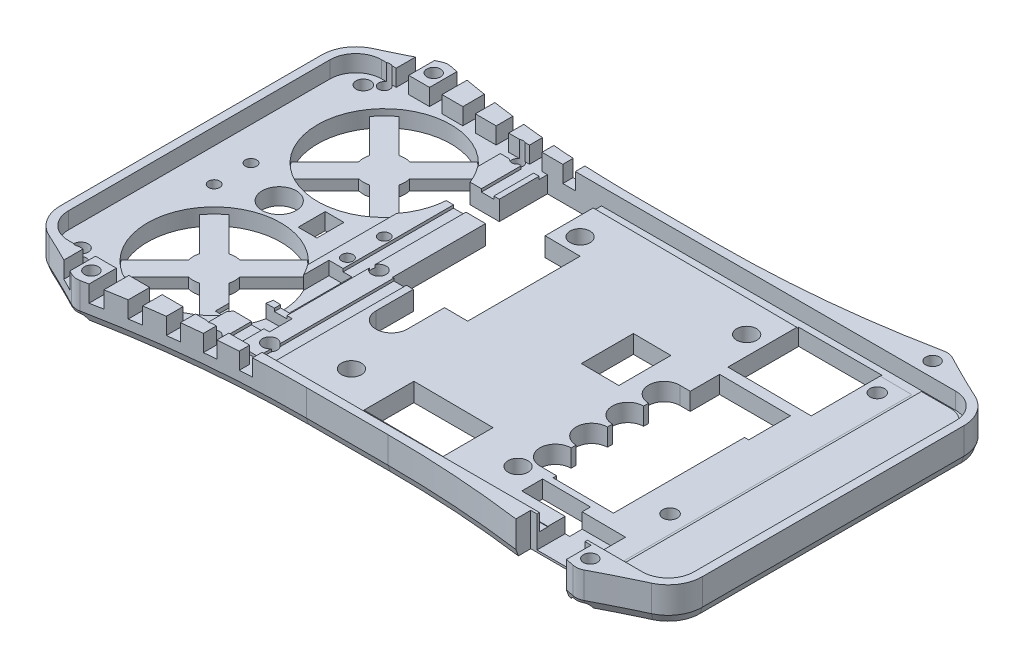
SolidWorks part; units mm, degrees
ref_plane "前视基准面" through (0, 0, 0) normal (0, 0, 1) x (1, 0, 0)
ref_plane "上视基准面" through (0, 0, 0) normal (0, 1, 0) x (1, 0, 0)
ref_plane "右视基准面" through (0, 0, 0) normal (1, 0, 0) x (0, 0, -1)
sketch "草图1" plane through (0, 0, 0) normal (0, 1, 0) x (1, 0, 0)
  line L0 (6, 0.2) -> (143.8, 0.2)
  line L1 (6, 0) -> (143.8, 0) construction
  line L2 (0, -6) -> (0, -68.8) construction
  line L3 (6, -74.8) -> (143.8, -74.8) construction
  line L4 (149.8, -6) -> (149.8, -68.8) construction
  line L5 (150, -6) -> (150, -68.8)
  line L6 (6, -75) -> (143.8, -75)
  line L7 (-0.2, -6) -> (-0.2, -68.8)
  arc A0 (143.8, 0) -> (149.8, -6) centre (143.8, -6) cw construction
  arc A1 (143.8, -74.8) -> (149.8, -68.8) centre (143.8, -68.8) ccw construction
  arc A2 (0, -68.8) -> (6, -74.8) centre (6, -68.8) ccw construction
  arc A3 (6, 0) -> (0, -6) centre (6, -6) ccw construction
  arc A4 (143.8, 0.2) -> (150, -6) centre (143.8, -6) cw
  arc A5 (143.8, -75) -> (150, -68.8) centre (143.8, -68.8) ccw
  arc A6 (-0.2, -68.8) -> (6, -75) centre (6, -68.8) ccw
  arc A7 (6, 0.2) -> (-0.2, -6) centre (6, -6) ccw
  point P7 (149.8, 0)
  point P12 (0, -74.8)
  point P15 (0, 0)
  dimension "D3" = 6
  dimension "D1" = 74.8
  dimension "D2" = 149.8
  dimension "D4" = 0.2
extrude "凸台-拉伸1" add sketch "草图1" along normal blind 4
sketch "草图2" plane through (0, 0, 0) normal (0, -1, 0) x (-1, 0, 0)
  line L0 (-122.6, -55.35) -> (-108.9, -55.35)
  line L1 (-122.6, -69.85) -> (-108.9, -69.85)
  line L2 (-122.6, -69.85) -> (-122.6, -63.95)
  line L3 (-122.6, -63.95) -> (-108.9, -63.95)
  line L4 (-108.9, -69.85) -> (-108.9, -63.95)
  line L5 (-135.3, -1.25) -> (-35.3, -1.25) construction
  line L6 (-135.3, -1.25) -> (-135.3, -73.55) construction
  line L7 (-135.3, -73.55) -> (-35.3, -73.55) construction
  line L8 (-35.3, -1.25) -> (-35.3, -73.55) construction
  line L9 (-108.9, -61.25) -> (-108.9, -55.35)
  line L10 (-122.6, -61.25) -> (-108.9, -61.25)
  line L11 (-122.6, -61.25) -> (-122.6, -55.35)
  line L12 (-122.6, -46.75) -> (-108.9, -46.75)
  line L13 (-108.9, -52.65) -> (-108.9, -46.75)
  line L14 (-122.6, -52.65) -> (-108.9, -52.65)
  line L15 (-122.6, -52.65) -> (-122.6, -46.75)
  line L16 (-122.6, -38.15) -> (-108.9, -38.15)
  line L17 (-108.9, -44.05) -> (-108.9, -38.15)
  line L18 (-122.6, -44.05) -> (-108.9, -44.05)
  line L19 (-122.6, -44.05) -> (-122.6, -38.15)
  line L20 (0, -6) -> (0, -68.8) construction
  line L21 (-35.3, -73.55) -> (-0.8, -73.55) construction
  line L22 (-120.25, -26.65) -> (-111.25, -26.65) construction
  line L23 (-120.25, -26.65) -> (-120.25, -33.15) construction
  line L24 (-120.25, -33.15) -> (-111.25, -33.15) construction
  line L25 (-111.25, -26.65) -> (-111.25, -33.15) construction
  line L26 (-85.8, -48.75) -> (-81.1, -48.75) construction
  line L27 (-85.8, -48.75) -> (-85.8, -58.15) construction
  line L28 (-85.8, -58.15) -> (-81.1, -58.15) construction
  line L29 (-81.1, -48.75) -> (-81.1, -58.15) construction
  line L30 (-71.5, -48.65) -> (-68.2, -48.65) construction
  line L31 (-71.5, -48.65) -> (-71.5, -57.55) construction
  line L32 (-71.5, -57.55) -> (-68.2, -57.55) construction
  line L33 (-68.2, -48.65) -> (-68.2, -57.55) construction
  line L34 (-43.1, -45.05) -> (-38.6, -45.05) construction
  line L35 (-43.1, -45.05) -> (-43.1, -59.05) construction
  line L36 (-43.1, -59.05) -> (-38.6, -59.05) construction
  line L37 (-38.6, -45.05) -> (-38.6, -59.05) construction
  line L38 (-45.3, -61.55) -> (-33.3, -61.55) construction
  line L39 (-45.3, -61.55) -> (-45.3, -66.05) construction
  line L40 (-45.3, -66.05) -> (-33.3, -66.05) construction
  line L41 (-33.3, -61.55) -> (-33.3, -66.05) construction
  line L42 (-0.8, -73.55) -> (-0.8, -1.25) construction
  line L43 (-0.8, -1.25) -> (-35.3, -1.25) construction
  line L44 (-149.8, -6) -> (-149.8, -68.8) construction
  line L45 (-30.8, -34.65) -> (-27.3, -34.65) construction
  line L46 (-30.8, -34.65) -> (-30.8, -40.15) construction
  line L47 (-30.8, -40.15) -> (-27.3, -40.15) construction
  line L48 (-27.3, -34.65) -> (-27.3, -40.15) construction
  line L49 (-120.75, -33.65) -> (-110.75, -33.65)
  line L50 (-110.75, -26.15) -> (-110.75, -33.65)
  line L51 (-120.75, -26.15) -> (-110.75, -26.15)
  line L52 (-120.75, -26.15) -> (-120.75, -33.65)
  line L53 (-86.3, -48.25) -> (-86.3, -58.65)
  line L54 (-86.3, -58.65) -> (-80.6, -58.65)
  line L55 (-80.6, -48.25) -> (-80.6, -58.65)
  line L56 (-86.3, -48.25) -> (-80.6, -48.25)
  line L57 (-72, -48.15) -> (-72, -58.05)
  line L58 (-72, -58.05) -> (-67.7, -58.05)
  line L59 (-67.7, -48.15) -> (-67.7, -58.05)
  line L60 (-72, -48.15) -> (-67.7, -48.15)
  line L61 (-31.3, -34.15) -> (-31.3, -40.65)
  line L62 (-31.3, -40.65) -> (-26.8, -40.65)
  line L63 (-26.8, -34.15) -> (-26.8, -40.65)
  line L64 (-31.3, -34.15) -> (-26.8, -34.15)
  line L65 (-43.6, -44.55) -> (-43.6, -59.55)
  line L66 (-43.6, -59.55) -> (-38.1, -59.55)
  line L67 (-38.1, -44.55) -> (-38.1, -59.55)
  line L68 (-43.6, -44.55) -> (-38.1, -44.55)
  line L69 (-45.8, -61.05) -> (-45.8, -66.55)
  line L70 (-45.8, -66.55) -> (-32.8, -66.55)
  line L71 (-32.8, -61.05) -> (-32.8, -66.55)
  line L72 (-45.8, -61.05) -> (-32.8, -61.05)
  circle A0 centre (-103.2, -9.35) radius 2 construction
  circle A1 centre (-103.2, -64.25) radius 2 construction
  circle A2 centre (-63.2, -64.25) radius 2 construction
  circle A3 centre (-63.2, -9.35) radius 2 construction
  circle A4 centre (-130.8, -5.6) radius 1.25 construction
  circle A5 centre (-131.1, -55.65) radius 1.25 construction
  circle A6 centre (-47.7, -4.85) radius 1.25 construction
  circle A7 centre (-48.1, -68.75) radius 1.25 construction
  circle A8 centre (-22.8, -70.3) radius 1.25 construction
  circle A9 centre (-5.05, -71.05) radius 1.25 construction
  circle A10 centre (-5.05, -3.25) radius 1.25 construction
  circle A11 centre (-19, -37.4) radius 3.6 construction
  circle A12 centre (-103.2, -9.35) radius 2.4
  circle A13 centre (-63.2, -9.35) radius 2.4
  circle A14 centre (-63.2, -64.25) radius 2.4
  circle A15 centre (-103.2, -64.25) radius 2.4
  circle A16 centre (-19, -37.4) radius 4.1
  circle A17 centre (-130.8, -5.6) radius 1.75
  circle A18 centre (-131.1, -55.65) radius 1.75
  circle A19 centre (-48.1, -68.75) radius 1.75
  circle A20 centre (-22.8, -70.3) radius 1.75
  circle A21 centre (-5.05, -71.05) radius 1.75
  circle A22 centre (-5.05, -3.25) radius 1.75
  circle A23 centre (-47.7, -4.85) radius 1.75
  circle A24 centre (-46.11, -40.57) radius 1.25 construction
  circle A25 centre (-46.11, -40.57) radius 1.75
  point P22 (0, -37.4)
  point P23 (-135.3, -37.4)
  point P28 (-115.75, -33.15)
  point P29 (-115.75, -38.15)
  point P30 (-111.25, -29.9)
  point P31 (-108.9, -41.1)
  point P79 (-0.8, -37.4)
  point P81 (-27.3, -37.4)
  dimension "D21" = 4
  dimension "D34" = 2.5
  dimension "D53" = 7.2
  dimension "D1" = 13.7
  dimension "D2" = 5.9
  dimension "D3" = 72.3
  dimension "D4" = 3.7
  dimension "D5" = 12.7
  dimension "D7" = 14.5
  dimension "D8" = 100
  dimension "D9" = 2.7
  dimension "D10" = 9
  dimension "D11" = 6.5
  dimension "D12" = 11.2
  dimension "D13" = 15.4
  dimension "D14" = 9.4
  dimension "D15" = 4.7
  dimension "D16" = 23.1
  dimension "D17" = 3.3
  dimension "D18" = 8.9
  dimension "D19" = 16
  dimension "D20" = 37.4
  dimension "D22" = 8.1
  dimension "D23" = 32.1
  dimension "D24" = 40
  dimension "D25" = 9.3
  dimension "D26" = 14
  dimension "D27" = 4.5
  dimension "D28" = 12
  dimension "D29" = 4.5
  dimension "D30" = 3.3
  dimension "D31" = 2
  dimension "D32" = 7.5
  dimension "D33" = 14.5
  dimension "D35" = 34.5
  dimension "D36" = 2
  dimension "D37" = 4.25
  dimension "D38" = 2.5
  dimension "D39" = 3.25
  dimension "D40" = 22
  dimension "D41" = 4.8
  dimension "D42" = 12.8
  dimension "D43" = 3.6
  dimension "D44" = 12.4
  dimension "D45" = 4.35
  dimension "D46" = 4.5
  dimension "D47" = 4.2
  dimension "D48" = 17.9
  dimension "D49" = 18.2
  dimension "D50" = 3.5
  dimension "D51" = 5.5
  dimension "D52" = 8.3
  dimension "D58" = 28.18
  dimension "D59" = 1.99
  dimension "D54" = 0.4
  dimension "D55" = 0.5
  dimension "D56" = 0.5
  dimension "D57" = 0.5
  dimension "D6" = 4
sketch "草图7" plane through (0, 0, -0.2) normal (0, 0, -1) x (-1, 0, 0)
  line L0 (-135.3, 4) -> (-35.3, 4.75)
  line L2 (-35.3, 4.75) -> (-35.3, 4)
  line L4 (-35.3, 4) -> (-135.3, 4)
  line L6 (-143.8, 4) -> (-6, 4) construction
  dimension "D1" = 0.75
extrude "凸台-拉伸11" add sketch "草图7" against normal offset from surface (71.2 mm away) 2 from offset 2 up to face at (74.9, 2, 75) offset against normal yes
extrude "切除-拉伸1" cut sketch "草图2" against normal blind 10 contours A12 | A13 | A14 | A15
sketch "草图3" plane through (0, 0, 0) normal (0, 1, 0) x (1, 0, 0)
  line L0 (136.8, -1) -> (136.8, -73.8)
  line L1 (143.8, 0) -> (135.8, 0) construction
  line L2 (149.8, -6) -> (149.8, -68.8) construction
  line L3 (143.8, -74.8) -> (135.8, -74.8) construction
  line L4 (135.8, 0) -> (135.8, -74.8) construction
  line L5 (6, -74.8) -> (143.8, -74.8) construction
  line L6 (135.3, -1.25) -> (135.3, -73.55) construction
  line L7 (143.8, -73.8) -> (136.8, -73.8)
  line L8 (148.8, -6) -> (148.8, -68.8)
  line L9 (143.8, -1) -> (136.8, -1)
  arc A0 (143.8, 0) -> (149.8, -6) centre (143.8, -6) cw construction
  arc A1 (149.8, -68.8) -> (143.8, -74.8) centre (143.8, -68.8) cw construction
  arc A2 (148.8, -68.8) -> (143.8, -73.8) centre (143.8, -68.8) cw
  arc A3 (143.8, -1) -> (148.8, -6) centre (143.8, -6) cw
  point P17 (149.8, 0)
  dimension "D1" = 6
  dimension "D2" = 0.5
  dimension "D3" = 1
extrude "凸台-拉伸9" add sketch "草图3" along normal offset from surface (5 mm away) 1 up to face at (85.3, 4, 37.4) offset beyond the face yes
sketch "草图4" plane through (0, 0, 0) normal (0, 1, 0) x (1, 0, 0)
  line L0 (125.2, -20.85) -> (108.2, -20.85)
  line L1 (108.2, -30.85) -> (109.7, -30.85)
  line L2 (109.7, -30.85) -> (109.7, -62.35)
  line L3 (108.7, -68.85) -> (108.7, -62.35)
  line L4 (49.2, -40.35) -> (49.2, -13.35)
  line L5 (108.2, -30.85) -> (108.2, -20.85)
  line L6 (108.7, -68.85) -> (120.2, -68.85)
  line L7 (108.2, -30.85) -> (125.2, -30.85) construction
  line L8 (109.7, -62.35) -> (124.2, -62.35)
  line L9 (80.466, -18.85) -> (96.6871, -18.85) construction
  line L10 (107.2, 11.628) -> (107.2, 24.7853) construction
  line L11 (49.2, -13.35) -> (67.2, -13.35)
  line L12 (125.2, -30.85) -> (124.2, -30.85)
  line L13 (124.2, -30.85) -> (124.2, -62.35)
  line L14 (124.2, -62.35) -> (120.2, -62.35)
  line L15 (120.2, -62.35) -> (120.2, -68.85)
  line L16 (67.2, -13.35) -> (67.2, -40.35)
  line L17 (67.2, -40.35) -> (49.2, -40.35)
  line L18 (63.2, -9.35) -> (46.0308, -9.35) construction
  line L19 (105.7, -55.55) -> (105.7, -28.85) construction
  line L20 (108.7, -63.85) -> (120.2, -63.85)
  line L21 (125.2, -20.85) -> (125.2, -30.85)
  line L22 (105.7, -27.9) -> (108.2, -27.9)
  line L23 (105.7, -35.4) -> (109.7, -35.4)
  line L24 (105.7, -36.6) -> (109.7, -36.6)
  line L25 (109.7, -36.6) -> (109.7, -44.1)
  line L26 (109.7, -44.1) -> (105.7, -44.1)
  line L27 (105.7, -45.3) -> (109.7, -45.3)
  line L28 (105.7, -52.8) -> (109.7, -52.8)
  line L29 (105.7, -54) -> (109.7, -54)
  line L30 (105.7, -61.5) -> (109.7, -61.5)
  line L31 (54.15, -49.35) -> (54.15, -40.35)
  line L32 (61.65, -49.35) -> (61.65, -40.35)
  line L33 (89.5, -35.35) -> (89.5, -22.85)
  line L34 (89.5, -22.85) -> (98.5, -22.85)
  line L35 (98.5, -22.85) -> (98.5, -35.35)
  line L36 (98.5, -35.35) -> (89.5, -35.35)
  line L37 (58.8, -1.85) -> (58.8, -13.85)
  line L38 (58.8, -13.85) -> (45.8, -13.85)
  line L39 (107.7, -18.35) -> (107.7, -1.35)
  line L40 (107.7, -1.35) -> (127.7, -1.35)
  line L41 (127.7, -1.35) -> (127.7, -18.35)
  line L42 (127.7, -18.35) -> (107.7, -18.35)
  line L43 (92.2, -59.25) -> (92.2, -71.25)
  line L44 (92.2, -71.25) -> (73.2, -71.25)
  line L45 (73.2, -71.25) -> (73.2, -59.25)
  line L46 (73.2, -59.25) -> (92.2, -59.25)
  line L47 (45.8, -13.85) -> (45.8, -1.85)
  line L48 (45.8, -1.85) -> (58.8, -1.85)
  line L49 (45.8, -11.35) -> (37.8, -11.35)
  line L50 (37.8, -11.35) -> (37.8, -18.05)
  line L51 (37.8, -18.05) -> (45.8, -18.05)
  line L52 (45.8, -18.05) -> (45.8, -11.35)
  line L53 (45.8, -18.05) -> (49.2, -18.05)
  line L54 (45.8, -1.85) -> (45.8, 0.2)
  line L55 (143.8, 0.2) -> (6, 0.2) construction
  line L56 (45.8, 0.2) -> (58.8, 0.2)
  line L57 (58.8, 0.2) -> (58.8, -1.85)
  line L59 (105.7, -54) -> (109.7, -54)
  line L60 (105.7, -54) -> (105.7, -52.8)
  line L61 (105.7, -52.8) -> (109.7, -52.8)
  line L62 (109.7, -54) -> (109.7, -52.8)
  line L63 (105.7, -45.3) -> (109.7, -45.3)
  line L64 (105.7, -45.3) -> (105.7, -44.1)
  line L65 (105.7, -44.1) -> (109.7, -44.1)
  line L66 (109.7, -45.3) -> (109.7, -44.1)
  line L67 (105.7, -36.6) -> (109.7, -36.6)
  line L68 (105.7, -36.6) -> (105.7, -35.4)
  line L69 (105.7, -35.4) -> (109.7, -35.4)
  line L70 (109.7, -36.6) -> (109.7, -35.4)
  circle A0 centre (103.2, -9.35) radius 2.4 construction
  circle A1 centre (103.2, -64.25) radius 2.4 construction
  circle A2 centre (103.2, -64.25) radius 2.4
  circle A3 centre (63.2, -64.25) radius 2.4 construction
  circle A4 centre (63.2, -64.25) radius 2.4
  circle A5 centre (103.2, -9.35) radius 2.4 construction
  circle A6 centre (105.7, -31.65) radius 3.75
  circle A7 centre (105.7, -40.35) radius 3.75
  circle A8 centre (105.7, -49.05) radius 3.75
  circle A9 centre (105.7, -57.75) radius 3.75
  circle A10 centre (63.2, -9.35) radius 2.4 construction
  circle A11 centre (63.2, -9.35) radius 2.4 construction
  circle A12 centre (57.9, -49.35) radius 3.75
  point P30 (67.2, -26.85)
  dimension "D7" = 9.5
  dimension "D30" = 4.5
  dimension "D40" = 7.5
  dimension "D18" = 7.5
  dimension "D21" = 4.5
  dimension "D4" = 11.5
  dimension "D5" = 48
  dimension "D6" = 10
  dimension "D8" = 4
  dimension "D9" = 5
  dimension "D10" = 5
  dimension "D11" = 17
  dimension "D12" = 6.5
  dimension "D13" = 1
  dimension "D14" = 14
  dimension "D15" = 18
  dimension "D16" = 4
  dimension "D17" = 27
  dimension "D19" = 40
  dimension "D20" = 5.3
  dimension "D22" = 4.4
  dimension "D23" = 13
  dimension "D24" = 1.5
  dimension "D25" = 12.5
  dimension "D26" = 5.5
  dimension "D27" = 9
  dimension "D28" = 8.7
  dimension "D29" = 12
  dimension "D31" = 20
  dimension "D32" = 9
  dimension "D33" = 17
  dimension "D34" = 11
  dimension "D35" = 19
  dimension "D36" = 12
  dimension "D37" = 7
  dimension "D38" = 11.5
  dimension "D39" = 22.3
  dimension "D41" = 2.5
  dimension "D43" = 13.5
  dimension "D44" = 4.7
  dimension "D45" = 8
  dimension "D46" = 2.5
  dimension "D47" = 6.7
  dimension "D42" = 4
extrude "拉伸-薄壁1" add sketch "草图1<2>" along normal blind 8 thin thin type one direction wall 2
sketch "草图1<2>" plane through (0, 0, 0) normal (0, 1, 0) x (1, 0, 0) same geometry as "草图1"
extrude "切除-拉伸2" cut sketch "草图4" along normal through all contours L20 L3 L6 L15 | A9 L30 L2 L29 | A8 L28 L2 L27 | A7 L26 L2 L24 | A6 L23 L2 L1 | A6 L5 L22 | A12 L17 L31 | A12 L32 L17 | L52 L53 L4 L38 | L57 L56 L54 L48 | L68 L24 L2 L23 | L64 L27 L2 L26 | L60 L29 L2 L28 | L41 L42 L39 L40 | L8 L2 L1 L5 L0 L21 L12 L13 | A6 | A7 | A8 | A9 | L46 L43 L44 L45 | L35 L36 L33 L34 | L4 L11 L16 L17 | A12 | L47 L48 L37 L38 | L50 L51 L52 L49 region at (114.45, 0, 66.35) region at (107.592, 0, 28.1789) region at (108.8789, 0, 34.1518) region at (107.7, 0, 36) region at (107.7, 0, 36.685) region at (107.7, 0, 44.7) region at (107.7, 0, 61.415) region at (107.7, 0, 45.385) region at (107.7, 0, 53.4) region at (47.5, 0, 15.95) region at (57.9, 0, 43.4352) region at (52.3, 0, 0.825)
extrude "切除-拉伸3" cut sketch "草图2<11>" against normal through all contours L61 L62 L63 L64 | A16
sketch "草图2<11>" plane through (0, 0, 0) normal (0, -1, 0) x (-1, 0, 0) same geometry as "草图2"
extrude "切除-拉伸4" cut sketch "草图2<13>" against normal through all contours A17 | A18 | A19 | A23 | A22 | A21 | A25
sketch "草图2<13>" plane through (0, 0, 0) normal (0, -1, 0) x (-1, 0, 0) same geometry as "草图2"
extrude "切除-拉伸5" cut sketch "草图2<14>" against normal through all from offset 1.5 contours L67 L66 L65 L68 | L71 L70 L69 L72 offset against normal yes
sketch "草图2<14>" plane through (0, 0, 0) normal (0, -1, 0) x (-1, 0, 0) same geometry as "草图2"
sketch "草图5" plane through (0, 0, 0) normal (0, -1, 0) x (-1, 0, 0)
  text T0 "<b>M3*6</b>" font "@Adobe 黑体 Std R" height 7
  text T1 "<b>M3*6</b>" font "@Adobe 黑体 Std R" height 7
  text T2 "<b>M3*6</b>" font "@Adobe 黑体 Std R" height 7
  text T3 "<b>M3*6</b>" font "@Adobe 黑体 Std R" height 7
extrude "切除-拉伸6" [suppressed] cut sketch "草图5" against normal blind 0.6
sketch "草图6" plane through (0, 0, 0) normal (0, 1, 0) x (1, 0, 0)
  line L1 (0, -6) -> (0, -68.8) construction
  line L2 (149.8, -6) -> (149.8, -68.8) construction
  line L4 (6, 0.2) -> (143.8, 0.2) construction
  line L5 (6, -75) -> (143.8, -75) construction
  circle A0 centre (15, 3.7) radius 1.5 construction
  circle A1 centre (15, -78.5) radius 1.5 construction
  circle A2 centre (134.8, 3.7) radius 1.5 construction
  circle A3 centre (134.8, -78.5) radius 1.5 construction
  circle A4 centre (15, 3.7) radius 3.5
  circle A5 centre (15, -78.5) radius 3.5
  circle A6 centre (134.8, 3.7) radius 3.5
  circle A7 centre (134.8, -78.5) radius 3.5
  circle A8 centre (15, 3.7) radius 1.65
  circle A9 centre (134.8, 3.7) radius 1.65
  circle A10 centre (134.8, -78.5) radius 1.65
  circle A11 centre (15, -78.5) radius 1.65
  dimension "D1" = 3
  dimension "D3" = 0.15
  dimension "D4" = 15
  dimension "D5" = 15
  dimension "D2" = 2
extrude "凸台-拉伸10" add sketch "草图6" along normal up to surface (8 mm away) up to face at (74.9, 8, 37.4)
extrude "切除-拉伸9" cut sketch "草图6<2>" along normal through all contours A8 | A9 | A10 | A11
sketch "草图6<2>" plane through (0, 0, 0) normal (0, 1, 0) x (1, 0, 0) same geometry as "草图6"
fillet "圆角1" radius 250 8 edges at (18.1623, 4, 77) (11.8377, 4, 77) (131.6377, 4, 77) (137.9623, 4, 77) (137.9623, 4, -2.2) (131.6377, 4, -2.2) (11.8377, 4, -2.2) (18.1623, 4, -2.2)
chamfer "倒角1" distance 0.6 angle 70 20 edges at (40.2731, 0, 78.2358) (14.5029, 0, 81.9645) (74.9, 0, 77) (7.988, 0, 78.8506) (109.5269, 0, 78.2358) (-0.9143, 0, 73.2083) (135.2971, 0, 81.9645) (-2.2, 0, 37.4) (141.812, 0, 78.8506) (-0.9143, 0, 1.5917) (150.7143, 0, 73.2083) (7.988, 0, -4.0506) (152, 0, 37.4) (14.5029, 0, -7.1645) (150.7143, 0, 1.5917) (40.2731, 0, -3.4358) (141.812, 0, -4.0506) (74.9, 0, -2.2) (135.2971, 0, -7.1645) (109.5269, 0, -3.4358) first distance on face at (134.8, 0, 80.15)
sketch "草图8" plane through (0, 0, 0) normal (0, -1, 0) x (1, 0, 0)
  line L0 (7.8, 32.9807) -> (7.8, 0.9807) construction
  line L1 (7.8, 0.9807) -> (39.8, 0.9807) construction
  line L2 (39.8, 0.9807) -> (39.8, 32.9807) construction
  line L3 (39.8, 32.9807) -> (7.8, 32.9807) construction
  line L4 (31.3, 37.4) -> (26.8, 37.4) construction
  line L5 (-2.2, 6) -> (-2.2, 68.8) construction
  line L7 (39.8, 41.8193) -> (7.8, 41.8193) construction
  line L8 (39.8, 73.8193) -> (39.8, 41.8193) construction
  line L9 (7.8, 73.8193) -> (39.8, 73.8193) construction
  line L10 (7.8, 41.8193) -> (7.8, 73.8193) construction
  circle A0 centre (39.8, 0.9807) radius 1.35
  circle A1 centre (39.8, 32.9807) radius 1.35
  circle A2 centre (7.8, 32.9807) radius 1.35
  circle A3 centre (7.8, 0.9807) radius 1.35
  circle A4 centre (7.8, 73.8193) radius 1.35
  circle A5 centre (7.8, 41.8193) radius 1.35
  circle A6 centre (39.8, 41.8193) radius 1.35
  circle A7 centre (39.8, 73.8193) radius 1.35
  point P4 (7.8, 16.9807)
  dimension "D3" = 10
  dimension "D6" = 2.7
  dimension "D1" = 32
  dimension "D2" = 32
extrude "切除-拉伸10" cut sketch "草图8" against normal through all
sketch "草图9" plane through (0, 0, 0) normal (0, -1, 0) x (1, 0, 0)
  line L0 (7.8, 32.9807) -> (39.8, 32.9807) construction
  line L1 (39.8, 32.9807) -> (39.8, 0.9807) construction
  line L2 (39.8, 0.9807) -> (7.8, 0.9807) construction
  line L3 (7.8, 0.9807) -> (7.8, 32.9807) construction
  line L4 (7.8, 32.9807) -> (39.8, 0.9807) construction
  line L5 (39.8, 32.9807) -> (7.8, 0.9807) construction
  line L6 (11.3355, 32.9807) -> (39.8, 4.5163)
  line L7 (39.8, 4.5163) -> (36.2645, 0.9807)
  line L8 (36.2645, 0.9807) -> (7.8, 29.4452)
  line L9 (7.8, 29.4452) -> (11.3355, 32.9807)
  line L10 (36.2645, 32.9807) -> (7.8, 4.5163)
  line L11 (7.8, 4.5163) -> (11.3355, 0.9807)
  line L12 (11.3355, 0.9807) -> (39.8, 29.4452)
  line L13 (39.8, 29.4452) -> (36.2645, 32.9807)
  line L14 (7.8, 0.9807) -> (39.8, 0.9807) construction
  line L15 (31.3, 37.4) -> (26.8, 37.4) construction
  line L18 (7.8, 73.8193) -> (39.8, 73.8193) construction
  line L19 (7.8, 41.8193) -> (39.8, 73.8193) construction
  line L20 (7.8, 73.8193) -> (7.8, 41.8193) construction
  line L21 (39.8, 73.8193) -> (7.8, 73.8193) construction
  line L22 (39.8, 41.8193) -> (39.8, 73.8193) construction
  line L23 (7.8, 41.8193) -> (39.8, 41.8193) construction
  line L24 (39.8, 45.3548) -> (36.2645, 41.8193)
  line L25 (11.3355, 73.8193) -> (39.8, 45.3548)
  line L26 (7.8, 70.2837) -> (11.3355, 73.8193)
  line L27 (36.2645, 41.8193) -> (7.8, 70.2837)
  line L28 (7.8, 45.3548) -> (11.3355, 41.8193)
  line L29 (36.2645, 73.8193) -> (7.8, 45.3548)
  line L30 (39.8, 70.2837) -> (36.2645, 73.8193)
  line L31 (11.3355, 41.8193) -> (39.8, 70.2837)
  line L32 (39.8, 41.8193) -> (7.8, 73.8193) construction
  circle A0 centre (23.8, 16.9807) radius 16
  circle A1 centre (23.8, 16.9807) radius 5
  circle A2 centre (23.8, 57.8193) radius 5
  circle A3 centre (23.8, 57.8193) radius 16
  dimension "D2" = 10
  dimension "D4" = 5
extrude "切除-拉伸11" cut sketch "草图9" against normal blind 10 contours A1 L10 A0 L6 | A1 L6 A0 L12 | A1 L12 A0 L8 | A1 L8 A0 L10 | A3 L29 A2 L27 | A3 L25 A2 L29 | A3 L31 A2 L25 | A3 L27 A2 L31 region at (23.8, 0, 28.2322) region at (12.5485, 0, 16.9807) region at (35.0515, 0, 16.9807) region at (23.8, 0, 5.7292) region at (35.0515, 0, 57.8193) region at (23.8, 0, 46.5678) region at (12.5485, 0, 57.8193) region at (23.8, 0, 69.0708)
sketch "草图10" plane through (0, 4, 0) normal (0, 1, 0) x (1, 0, 0)
  circle A0 centre (23.8, -16.9807) radius 16
  circle A1 centre (23.8, -57.8193) radius 16
  dimension "D1" = 32
  dimension "D2" = 32
extrude "切除-拉伸12" cut sketch "草图10" against normal mid plane 3
sketch "草图11" plane through (0, 8, 0) normal (0, 1, 0) x (1, 0, 0)
  line L0 (119.1, -85.85) -> (119.1, -65.85)
  line L1 (119.1, -65.85) -> (130.6, -65.85)
  line L2 (130.6, -65.85) -> (130.6, -85.85)
  line L3 (130.6, -85.85) -> (119.1, -85.85)
  line L4 (120.2, -63.85) -> (108.7, -63.85) construction
  circle A0 centre (131.1, -55.65) radius 1.75 construction
  circle A1 centre (131.1, -55.65) radius 1.75 construction
  dimension "D1" = 11.5
  dimension "D2" = 0.5
  dimension "D3" = 2
  dimension "D4" = 20
extrude "切除-拉伸13" cut sketch "草图11" against normal blind 4.5 from surface starting at face at (143.4785, 5, 37.4)
sketch "草图12" plane through (0, 8, 0) normal (0, 1, 0) x (1, 0, 0)
  line L0 (117.6, -75.6) -> (117.6, -88.4406)
  line L1 (117.6, -88.4406) -> (132.1, -88.4406)
  line L2 (132.1, -88.4406) -> (132.1, -75.6)
  line L3 (132.1, -75.6) -> (117.6, -75.6)
  line L4 (40.4545, -75) -> (143.8, -75) construction
  line L5 (119.1, -73) -> (119.1, -75) construction
  line L6 (130.6, -75) -> (130.6, -73) construction
  dimension "D1" = 0.6
  dimension "D2" = 1.5
  dimension "D3" = 1.5
extrude "切除-拉伸14" cut sketch "草图12" against normal through all
sketch "草图13" plane through (0, 0, 75.6) normal (0, 0, 1) x (1, 0, 0)
  line L0 (130.6, 5) -> (130.6, 8)
  line L1 (132.1, 8) -> (117.6, 8) construction
  line L2 (130.6, 8) -> (119.1, 8)
  line L3 (119.1, 8) -> (119.1, 5)
  line L4 (119.1, 5) -> (130.6, 5)
extrude "切除-拉伸15" cut sketch "草图13" against normal up to next
sketch "草图14" plane through (0, 0, 0) normal (0, -1, 0) x (1, 0, 0)
  circle A0 centre (15, 78.5) radius 3.25
  circle A1 centre (15, -3.7) radius 3.25
  circle A2 centre (134.8, -3.7) radius 3.25
  circle A3 centre (134.8, 78.5) radius 3.25
  dimension "D1" = 6.5
extrude "切除-拉伸16" cut sketch "草图14" against normal blind 3
sketch "草图15" plane through (0, 8, 0) normal (0, 1, 0) x (1, 0, 0)
  line L0 (-2.2, -6) -> (-2.2, -68.8) construction
  line L1 (9.5, 15.1483) -> (12.5, 15.1483)
  line L2 (9.5, 15.1483) -> (9.5, -93.5717)
  line L3 (9.5, -93.5717) -> (12.5, -93.5717)
  line L4 (12.5, 15.1483) -> (12.5, -93.5717)
  line L5 (17.5, 15.1483) -> (17.5, -93.5717)
  line L6 (17.5, 15.1483) -> (20.5, 15.1483)
  line L7 (20.5, 15.1483) -> (20.5, -93.5717)
  line L8 (17.5, -93.5717) -> (20.5, -93.5717)
  line L9 (25.5, 15.1483) -> (25.5, -93.5717)
  line L10 (25.5, 15.1483) -> (28.5, 15.1483)
  line L11 (28.5, 15.1483) -> (28.5, -93.5717)
  line L12 (25.5, -93.5717) -> (28.5, -93.5717)
  line L13 (33.5, 15.1483) -> (33.5, -93.5717)
  line L14 (33.5, 15.1483) -> (36.5, 15.1483)
  line L15 (36.5, 15.1483) -> (36.5, -93.5717)
  line L16 (33.5, -93.5717) -> (36.5, -93.5717)
  line L17 (41.5, 15.1483) -> (41.5, -93.5717)
  line L18 (41.5, 15.1483) -> (44.5, 15.1483)
  line L19 (44.5, 15.1483) -> (44.5, -93.5717)
  line L20 (41.5, -93.5717) -> (44.5, -93.5717)
  line L21 (49.5, 15.1483) -> (49.5, -93.5717)
  line L22 (49.5, 15.1483) -> (52.5, 15.1483)
  line L23 (52.5, 15.1483) -> (52.5, -93.5717)
  line L24 (49.5, -93.5717) -> (52.5, -93.5717)
  dimension "D1" = 3
  dimension "D2" = 11.7
  dimension "D3" = 6
extrude "切除-拉伸17" cut sketch "草图15" against normal blind 4
equation "\"D1@草图3\"=\"D3@草图1\""
